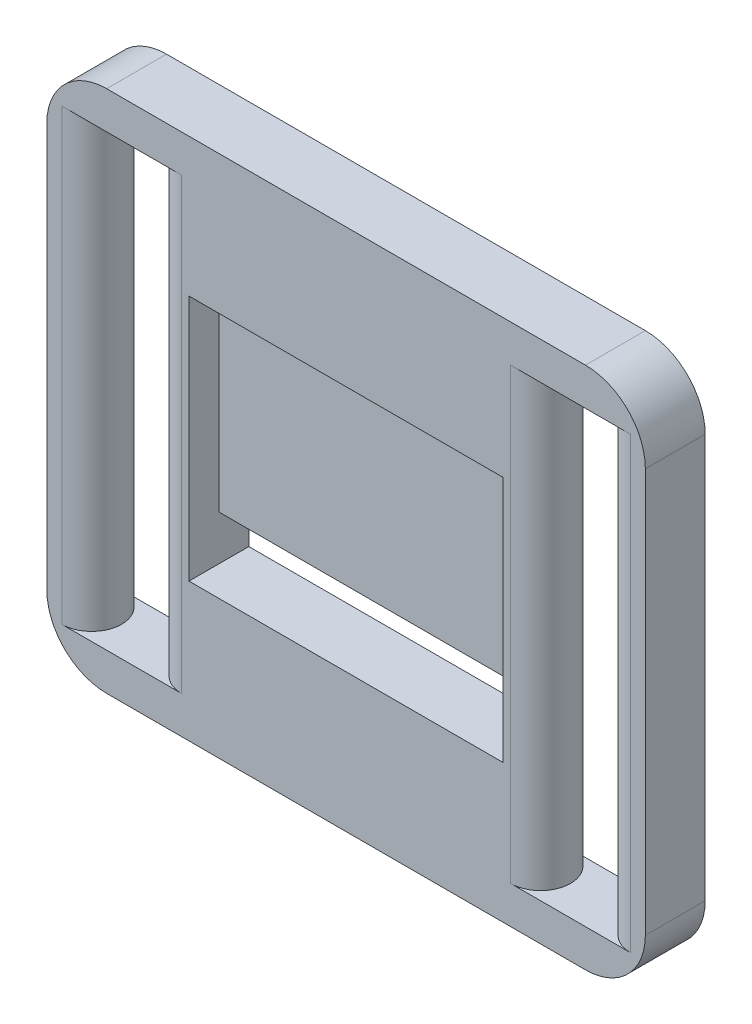
SolidWorks part; units mm, degrees
ref_plane "Plan de face" through (0, 0, 0) normal (0, 0, 1) x (1, 0, 0)
ref_plane "Plan de dessus" through (0, 0, 0) normal (0, 1, 0) x (1, 0, 0)
ref_plane "Plan de droite" through (0, 0, 0) normal (1, 0, 0) x (0, 0, -1)
sketch "Esquisse1" plane through (0, 0, 0) normal (0, 0, 1) x (1, 0, 0)
  line L1 (0, 0) -> (40, 0)
  line L2 (0, 0) -> (0, 35)
  line L3 (0, 35) -> (40, 35)
  line L4 (40, 0) -> (40, 35)
  dimension "D1" = 40
  dimension "D2" = 35
extrude "Boss.-Extru.1" add sketch "Esquisse1" along normal blind 4
sketch "Esquisse2" plane through (0, 0, 4) normal (0, 0, 1) x (1, 0, 0)
  line L0 (0, 35) -> (0, 0) construction
  line L1 (9.5, 25.75) -> (30.5, 25.75)
  line L2 (9.5, 25.75) -> (9.5, 9.25)
  line L3 (9.5, 9.25) -> (30.5, 9.25)
  line L4 (30.5, 25.75) -> (30.5, 9.25)
  line L5 (0, 0) -> (40, 0) construction
  dimension "D1" = 21
  dimension "D2" = 16.5
  dimension "D3" = 9.5
  dimension "D4" = 9.25
extrude "Enlèv. mat.-Extru.1" cut sketch "Esquisse2" against normal blind 2
sketch "Esquisse3" plane through (0, 0, 4) normal (0, 0, 1) x (1, 0, 0)
  line L0 (0, 35) -> (0, 0) construction
  line L1 (3, 32.5) -> (7, 32.5)
  line L2 (3, 32.5) -> (3, 2.5)
  line L3 (3, 2.5) -> (7, 2.5)
  line L4 (7, 32.5) -> (7, 2.5)
  line L5 (40, 35) -> (0, 35) construction
  line L6 (0, 0) -> (40, 0) construction
  line L7 (20, 35) -> (20, 0) construction
  line L8 (37, 32.5) -> (33, 32.5)
  line L9 (37, 32.5) -> (37, 2.5)
  line L10 (37, 2.5) -> (33, 2.5)
  line L11 (33, 32.5) -> (33, 2.5)
  line L12 (9.5, 25.75) -> (9.5, 9.25) construction
  line L13 (9.5, 12.25) -> (30.5, 12.25)
  line L14 (9.5, 12.25) -> (9.5, 9.25)
  line L15 (9.5, 9.25) -> (30.5, 9.25)
  line L16 (30.5, 12.25) -> (30.5, 9.25)
  line L17 (30.5, 9.25) -> (30.5, 25.75) construction
  line L18 (9.5, 9.25) -> (30.5, 9.25) construction
  dimension "D1" = 4
  dimension "D2" = 30
  dimension "D3" = 3
  dimension "D4" = 2.5
  dimension "D5" = 3
  dimension "D6" = 0
  dimension "D7" = 0
  dimension "D8" = 0
extrude "Enlèv. mat.-Extru.2" cut sketch "Esquisse3" against normal blind 6
fillet "Congé4" radius 4 4 edges at (40, 0, 2) (40, 35, 2) (0, 35, 2) (0, 0, 2) tangent propagation no
fillet "Congé6" 2 edges at (37, 17.5, 4) (37, 17.5, 0) type full round first side face at (35, 17.5, 4) second side face at (20, 10.75, 0) middle face at (37, 17.5, 2)
fillet "Congé7" 2 edges at (3, 17.5, 4) (3, 17.5, 0) type full round first side face at (36, 17.5, 4) second side face at (20, 10.75, 0) middle face at (3, 17.5, 2)
fillet "Congé8" 2 edges at (33, 17.5, 4) (33, 17.5, 0) type full round first side face at (36, 17.5, 4) second side face at (20, 10.75, 0) middle face at (33, 17.5, 2)
fillet "Congé9" 2 edges at (7, 17.5, 4) (7, 17.5, 0) type full round first side face at (35, 17.5, 4) second side face at (20, 10.75, 0) middle face at (7, 17.5, 2)
